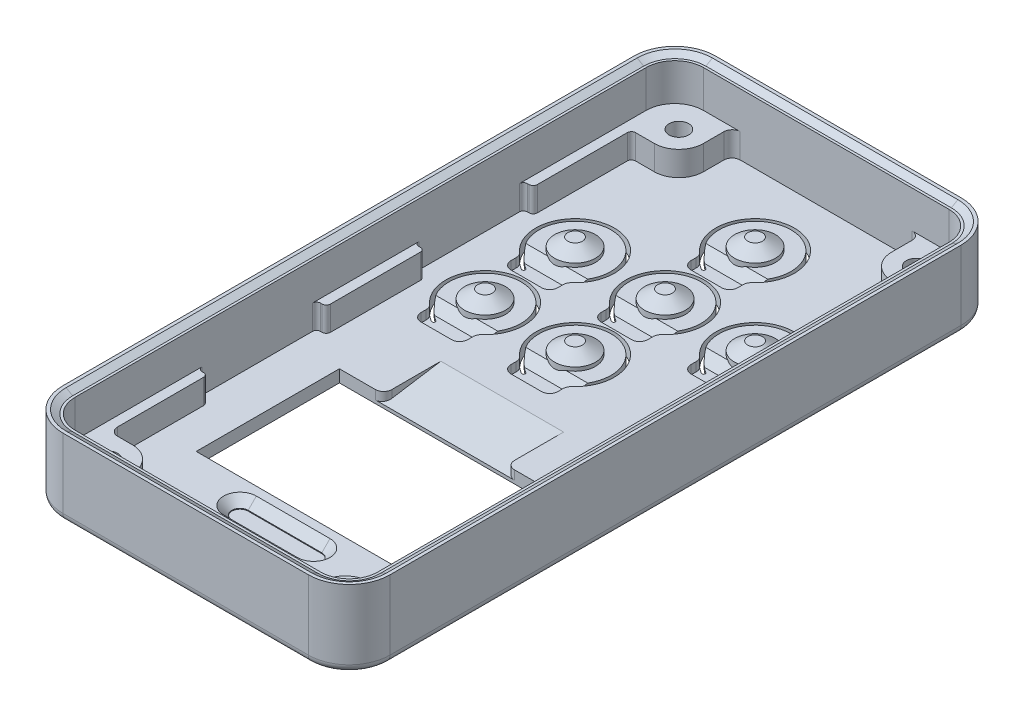
SolidWorks part; units mm, degrees
ref_plane "Front Plane" through (0, 0, 0) normal (0, 0, 1) x (1, 0, 0)
ref_plane "Top Plane" through (0, 0, 0) normal (0, 1, 0) x (1, 0, 0)
ref_plane "Right Plane" through (0, 0, 0) normal (1, 0, 0) x (0, 0, -1)
sketch "Base Sketch" plane through (0, 0, 0) normal (0, 1, 0) x (1, 0, 0)
  line L0 (0, 0) -> (40, 0)
  line L1 (40, 0) -> (40, 79.79)
  line L2 (40, 79.79) -> (0, 79.79)
  line L3 (0, 79.79) -> (0, 0)
extrude "Base" add sketch "Base Sketch" along normal blind 9.5
fillet "Corner Rounds R5" radius 5 4 edges at (0, 4.75, -79.79) (40, 4.75, -79.79) (40, 4.75, 0) (0, 4.75, 0)
shell "Shell 1.5" thickness 1.5 removed face at (20, 9.5, -39.895)
sketch "Boss Sketch" plane through (0, 0, 0) normal (0, 1, 0) x (1, 0, 0)
  line L0 (1.5, 1.5) -> (8.5, 1.5)
  line L1 (8.5, 1.5) -> (8.5, 5)
  line L2 (5.5, 8) -> (1.5, 8)
  line L3 (1.5, 8) -> (1.5, 1.5)
  line L4 (38.5, 1.5) -> (31.5, 1.5)
  line L5 (31.5, 1.5) -> (31.5, 5)
  line L6 (34.5, 8) -> (38.5, 8)
  line L7 (38.5, 8) -> (38.5, 1.5)
  line L16 (1.5, 78.29) -> (8.5, 78.29)
  line L17 (8.5, 78.29) -> (8.5, 74.79)
  line L18 (5.5, 71.79) -> (1.5, 71.79)
  line L19 (1.5, 71.79) -> (1.5, 78.29)
  line L20 (38.5, 78.29) -> (31.5, 78.29)
  line L21 (31.5, 78.29) -> (31.5, 74.79)
  line L22 (34.5, 71.79) -> (38.5, 71.79)
  line L23 (38.5, 71.79) -> (38.5, 78.29)
  arc A0 (8.5, 5) -> (5.5, 8) centre (5.4999, 4.9999) ccw
  circle A1 centre (5.5, 5) radius 1
  arc A2 (31.5, 5) -> (34.5, 8) centre (34.5001, 4.9999) cw
  circle A3 centre (34.5, 5) radius 1
  circle A5 centre (5.5, 74.79) radius 1
  circle A7 centre (34.5, 74.79) radius 1
  arc A8 (8.5, 74.79) -> (5.5, 71.79) centre (5.4999, 74.7901) cw
  arc A9 (31.5, 74.79) -> (34.5, 71.79) centre (34.5001, 74.7901) ccw
extrude "Corner Bosses (stop at ledge y4.5) + M2 Holes" add sketch "Boss Sketch" along normal blind 4.5
sketch "Ledge Sketch" plane through (0, 0, 0) normal (0, 1, 0) x (1, 0, 0)
  line L0 (1.5, 8) -> (2.7, 8)
  line L1 (2.7, 8) -> (2.7, 20)
  line L2 (2.7, 20) -> (1.5, 20)
  line L3 (1.5, 20) -> (1.5, 8)
  line L4 (37.3, 8) -> (38.5, 8)
  line L5 (38.5, 8) -> (38.5, 20)
  line L6 (38.5, 20) -> (37.3, 20)
  line L7 (37.3, 20) -> (37.3, 8)
  line L8 (1.5, 34.5) -> (2.7, 34.5)
  line L9 (2.7, 34.5) -> (2.7, 46.5)
  line L10 (2.7, 46.5) -> (1.5, 46.5)
  line L11 (1.5, 46.5) -> (1.5, 34.5)
  line L12 (37.3, 34.5) -> (38.5, 34.5)
  line L13 (38.5, 34.5) -> (38.5, 46.5)
  line L14 (38.5, 46.5) -> (37.3, 46.5)
  line L15 (37.3, 46.5) -> (37.3, 34.5)
  line L16 (1.5, 59.79) -> (2.7, 59.79)
  line L17 (2.7, 59.79) -> (2.7, 71.79)
  line L18 (2.7, 71.79) -> (1.5, 71.79)
  line L19 (1.5, 71.79) -> (1.5, 59.79)
  line L20 (37.3, 59.79) -> (38.5, 59.79)
  line L21 (38.5, 59.79) -> (38.5, 71.79)
  line L22 (38.5, 71.79) -> (37.3, 71.79)
  line L23 (37.3, 71.79) -> (37.3, 59.79)
extrude "Side Ledges" add sketch "Ledge Sketch" along normal blind 4.5
fillet "Outer Face Round R1" radius 1 8 edges at (1.4645, 0, -1.4645) (20, 0, 0) (38.5355, 0, -1.4645) (40, 0, -39.895) (38.5355, 0, -78.3255) (20, 0, -79.79) (1.4645, 0, -78.3255) (0, 0, -39.895)
sketch "Window Sketch" plane through (0, 0, 0) normal (0, 1, 0) x (1, 0, 0)
  line L0 (7.1, 14.5) -> (32.9, 14.5)
  line L1 (32.9, 14.5) -> (32.9, 31.7)
  line L2 (32.9, 31.7) -> (7.1, 31.7)
  line L3 (7.1, 31.7) -> (7.1, 14.5)
extrude "Display Window" cut sketch "Window Sketch" along normal through all
ref_plane "Mid Plane X20" through (20, 0, 0) normal (1, 0, 0) x (0, 0, -1)
sketch "Ramp Sketch" plane through (20, 0, 0) normal (1, 0, 0) x (0, 0, -1)
  line L0 (31, 0.4) -> (31.7, 0.4)
  line L1 (31.7, 0.4) -> (38.7, 1.5)
  line L2 (38.7, 1.5) -> (38.7, 2.5)
  line L3 (38.7, 2.5) -> (31, 2.5)
  line L4 (31, 2.5) -> (31, 0.4)
extrude "Cable Ramp" cut sketch "Ramp Sketch" against normal blind 7.5 and the other way blind 7.5
ref_plane "Plate Inner Face" through (0, 1.5, 0) normal (0, 1, 0) x (1, 0, 0)
sketch "LED Window Sketch" plane through (0, 1.5, 0) normal (0, 1, 0) x (1, 0, 0)
  circle A0 centre (20, 7.28) radius 1.7
  dimension "D1" = 3.4
extrude "LED Window" cut sketch "LED Window Sketch" against normal blind 1.1
sketch "Plunger Stems Sketch" plane through (0, 1.5, 0) normal (0, 1, 0) x (1, 0, 0)
  circle A0 centre (9, 47.6) radius 2.5
  circle A1 centre (20, 47.6) radius 2.5
  circle A2 centre (9, 58.6) radius 2.5
  circle A3 centre (20, 58.6) radius 2.5
  circle A4 centre (31, 58.6) radius 2.5
  circle A5 centre (20, 69.6) radius 2.5
extrude "Plunger Stems 5.0" add sketch "Plunger Stems Sketch" along normal blind 0.45
ref_plane "Plunger Cone Base" through (0, 1.95, 0) normal (0, 1, 0) x (1, 0, 0)
sketch "Plunger Cone Sketch" plane through (0, 1.95, 0) normal (0, 1, 0) x (1, 0, 0)
  circle A0 centre (9, 47.6) radius 2.5
  circle A1 centre (20, 47.6) radius 2.5
  circle A2 centre (9, 58.6) radius 2.5
  circle A3 centre (20, 58.6) radius 2.5
  circle A4 centre (31, 58.6) radius 2.5
  circle A5 centre (20, 69.6) radius 2.5
extrude "Plunger Cones to 1.8" add sketch "Plunger Cone Sketch" along normal blind 1 draft 57.995
fillet "Boss Junction Fillets R1" radius 1 7 edges at (37.3, 3, -71.79) (37.3, 3, -8) (2.7, 3, -8) (31.5, 3, -78.29) (8.5, 3, -78.29) (31.5, 3, -1.5) (8.5, 3, -1.5)
sketch "C-Slot Sketch" plane through (0, 0, 0) normal (0, 1, 0) x (1, 0, 0)
  arc A0 (10.4434, 43.0222) -> (7.5566, 43.0222) centre (9, 47.6) ccw
  arc A1 (7.5566, 43.0222) -> (7.6769, 43.4036) centre (7.6168, 43.2129) ccw
  arc A2 (7.6769, 43.4036) -> (10.3231, 43.4036) centre (9, 47.6) cw
  arc A3 (10.3231, 43.4036) -> (10.4434, 43.0222) centre (10.3832, 43.2129) ccw
  arc A4 (21.4434, 43.0222) -> (18.5566, 43.0222) centre (20, 47.6) ccw
  arc A5 (18.5566, 43.0222) -> (18.6769, 43.4036) centre (18.6168, 43.2129) ccw
  arc A6 (18.6769, 43.4036) -> (21.3231, 43.4036) centre (20, 47.6) cw
  arc A7 (21.3231, 43.4036) -> (21.4434, 43.0222) centre (21.3832, 43.2129) ccw
  arc A8 (10.4434, 54.0222) -> (7.5566, 54.0222) centre (9, 58.6) ccw
  arc A9 (7.5566, 54.0222) -> (7.6769, 54.4036) centre (7.6168, 54.2129) ccw
  arc A10 (7.6769, 54.4036) -> (10.3231, 54.4036) centre (9, 58.6) cw
  arc A11 (10.3231, 54.4036) -> (10.4434, 54.0222) centre (10.3832, 54.2129) ccw
  arc A12 (21.4434, 54.0222) -> (18.5566, 54.0222) centre (20, 58.6) ccw
  arc A13 (18.5566, 54.0222) -> (18.6769, 54.4036) centre (18.6168, 54.2129) ccw
  arc A14 (18.6769, 54.4036) -> (21.3231, 54.4036) centre (20, 58.6) cw
  arc A15 (21.3231, 54.4036) -> (21.4434, 54.0222) centre (21.3832, 54.2129) ccw
  arc A16 (32.4434, 54.0222) -> (29.5566, 54.0222) centre (31, 58.6) ccw
  arc A17 (29.5566, 54.0222) -> (29.6769, 54.4036) centre (29.6168, 54.2129) ccw
  arc A18 (29.6769, 54.4036) -> (32.3231, 54.4036) centre (31, 58.6) cw
  arc A19 (32.3231, 54.4036) -> (32.4434, 54.0222) centre (32.3832, 54.2129) ccw
  arc A20 (21.4434, 65.0222) -> (18.5566, 65.0222) centre (20, 69.6) ccw
  arc A21 (18.5566, 65.0222) -> (18.6769, 65.4036) centre (18.6168, 65.2129) ccw
  arc A22 (18.6769, 65.4036) -> (21.3231, 65.4036) centre (20, 69.6) cw
  arc A23 (21.3231, 65.4036) -> (21.4434, 65.0222) centre (21.3832, 65.2129) ccw
sketch "Sketch10" plane through (0, 1.5, 0) normal (0, 1, 0) x (1, 0, 0)
  line L0 (11.864, 44.259) -> (11.864, 41.636)
  line L1 (11.864, 41.636) -> (6.136, 41.636)
  line L2 (6.136, 41.636) -> (6.136, 44.259)
  line L3 (6.136, 44.259) -> (11.864, 44.259)
  line L4 (22.864, 44.259) -> (22.864, 41.636)
  line L5 (22.864, 41.636) -> (17.136, 41.636)
  line L6 (17.136, 41.636) -> (17.136, 44.259)
  line L7 (17.136, 44.259) -> (22.864, 44.259)
  line L8 (11.864, 55.259) -> (11.864, 52.636)
  line L9 (11.864, 52.636) -> (6.136, 52.636)
  line L10 (6.136, 52.636) -> (6.136, 55.259)
  line L11 (6.136, 55.259) -> (11.864, 55.259)
  line L12 (22.864, 55.259) -> (22.864, 52.636)
  line L13 (22.864, 52.636) -> (17.136, 52.636)
  line L14 (17.136, 52.636) -> (17.136, 55.259)
  line L15 (17.136, 55.259) -> (22.864, 55.259)
  line L16 (33.864, 55.259) -> (33.864, 52.636)
  line L17 (33.864, 52.636) -> (28.136, 52.636)
  line L18 (28.136, 52.636) -> (28.136, 55.259)
  line L19 (28.136, 55.259) -> (33.864, 55.259)
  line L20 (22.864, 66.259) -> (22.864, 63.636)
  line L21 (22.864, 63.636) -> (17.136, 63.636)
  line L22 (17.136, 63.636) -> (17.136, 66.259)
  line L23 (17.136, 66.259) -> (22.864, 66.259)
extrude "Cut-Extrude7" cut sketch "Sketch10" against normal blind 1.1
sketch "Sketch11" plane through (0, 0, 0) normal (0, 1, 0) x (1, 0, 0)
  arc A0 (11.4, 43.4431) -> (6.6, 43.4431) centre (9, 47.6) ccw
  arc A1 (6.6, 43.4431) -> (6.8, 43.7895) centre (6.7, 43.6163) ccw
  arc A2 (6.8, 43.7895) -> (11.2, 43.7895) centre (9, 47.6) cw
  arc A3 (11.2, 43.7895) -> (11.4, 43.4431) centre (11.3, 43.6163) ccw
  arc A4 (22.4, 43.4431) -> (17.6, 43.4431) centre (20, 47.6) ccw
  arc A5 (17.6, 43.4431) -> (17.8, 43.7895) centre (17.7, 43.6163) ccw
  arc A6 (17.8, 43.7895) -> (22.2, 43.7895) centre (20, 47.6) cw
  arc A7 (22.2, 43.7895) -> (22.4, 43.4431) centre (22.3, 43.6163) ccw
  arc A8 (11.4, 54.4431) -> (6.6, 54.4431) centre (9, 58.6) ccw
  arc A9 (6.6, 54.4431) -> (6.8, 54.7895) centre (6.7, 54.6163) ccw
  arc A10 (6.8, 54.7895) -> (11.2, 54.7895) centre (9, 58.6) cw
  arc A11 (11.2, 54.7895) -> (11.4, 54.4431) centre (11.3, 54.6163) ccw
  arc A12 (22.4, 54.4431) -> (17.6, 54.4431) centre (20, 58.6) ccw
  arc A13 (17.6, 54.4431) -> (17.8, 54.7895) centre (17.7, 54.6163) ccw
  arc A14 (17.8, 54.7895) -> (22.2, 54.7895) centre (20, 58.6) cw
  arc A15 (22.2, 54.7895) -> (22.4, 54.4431) centre (22.3, 54.6163) ccw
  arc A16 (33.4, 54.4431) -> (28.6, 54.4431) centre (31, 58.6) ccw
  arc A17 (28.6, 54.4431) -> (28.8, 54.7895) centre (28.7, 54.6163) ccw
  arc A18 (28.8, 54.7895) -> (33.2, 54.7895) centre (31, 58.6) cw
  arc A19 (33.2, 54.7895) -> (33.4, 54.4431) centre (33.3, 54.6163) ccw
  arc A20 (22.4, 65.4431) -> (17.6, 65.4431) centre (20, 69.6) ccw
  arc A21 (17.6, 65.4431) -> (17.8, 65.7895) centre (17.7, 65.6163) ccw
  arc A22 (17.8, 65.7895) -> (22.2, 65.7895) centre (20, 69.6) cw
  arc A23 (22.2, 65.7895) -> (22.4, 65.4431) centre (22.3, 65.6163) ccw
extrude "Button C-Slots 300deg 0.4" cut sketch "Sketch11" along normal through all
chamfer "Chamfer1" distance 1.1 angle 45 6 edges at (9, 1.5, -44.259) (20, 1.5, -66.259) (31, 1.5, -55.259) (20, 1.5, -55.259) (9, 1.5, -55.259) (20, 1.5, -44.259)
fillet "Fillet1" radius 1 24 edges at (11.864, 0.95, -43.7481) (11.864, 0.95, -41.636) (6.136, 0.95, -41.636) (6.136, 0.95, -43.7481) (22.864, 0.95, -63.636) (22.864, 0.95, -65.7481) (17.136, 0.95, -63.636) (17.136, 0.95, -65.7481) (33.864, 0.95, -52.636) (33.864, 0.95, -54.7481) (28.136, 0.95, -52.636) (28.136, 0.95, -54.7481) (22.864, 0.95, -52.636) (22.864, 0.95, -54.7481) (17.136, 0.95, -52.636) (17.136, 0.95, -54.7481) (11.864, 0.95, -52.636) (11.864, 0.95, -54.7481) (6.136, 0.95, -52.636) (6.136, 0.95, -54.7481) (22.864, 0.95, -41.636) (22.864, 0.95, -43.7481) (17.136, 0.95, -41.636) (17.136, 0.95, -43.7481)
fillet "Fillet2" radius 0.5 17 edges at (2.7, 3, -71.79) (1.5, 3, -59.79) (2.7, 3, -59.79) (38.5, 3, -59.79) (37.3, 3, -59.79) (38.5, 3, -46.5) (37.3, 3, -46.5) (2.7, 3, -46.5) (1.5, 3, -46.5) (38.5, 3, -34.5) (37.3, 3, -34.5) (2.7, 3, -34.5) (1.5, 3, -34.5) (38.5, 3, -20) (37.3, 3, -20) (2.7, 3, -20) (1.5, 3, -20)
fillet "Fillet3" radius 1 2 edges at (27.5, 0.95, -31.7) (12.5, 0.95, -31.7)
sketch "Button Symbols Cut Sketch" plane through (0, 0, 0) normal (0, 1, 0) x (1, 0, 0)
  line L0 (7.0908, 45.6908) -> (7.7272, 46.3272)
  line L1 (10.2728, 46.3272) -> (10.9092, 45.6908)
  line L2 (8.55, 47.2) -> (9.45, 47.2)
  line L3 (9.45, 47.2) -> (9.45, 44.4)
  line L4 (9.45, 44.4) -> (8.55, 44.4)
  line L5 (8.55, 44.4) -> (8.55, 47.2)
  line L6 (20, 44.8) -> (22.4249, 49)
  line L7 (22.4249, 49) -> (17.5751, 49)
  line L8 (17.5751, 49) -> (20, 44.8)
  line L9 (6.2, 58.6) -> (10.4, 56.1751)
  line L10 (10.4, 56.1751) -> (10.4, 61.0249)
  line L11 (10.4, 61.0249) -> (6.2, 58.6)
  line L12 (33.8, 58.6) -> (29.6, 61.0249)
  line L13 (29.6, 61.0249) -> (29.6, 56.1751)
  line L14 (29.6, 56.1751) -> (33.8, 58.6)
  line L15 (20, 72.4) -> (17.5751, 68.2)
  line L16 (17.5751, 68.2) -> (22.4249, 68.2)
  line L17 (22.4249, 68.2) -> (20, 72.4)
  arc A0 (10.9092, 45.6908) -> (7.0908, 45.6908) centre (9, 47.6) ccw
  arc A1 (7.7272, 46.3272) -> (10.2728, 46.3272) centre (9, 47.6) cw
  circle A2 centre (20, 58.6) radius 2.4
  circle A3 centre (20, 58.6) radius 1.5
sketch "Button Symbols Inlay Sketch" plane through (0, 0, 0) normal (0, 1, 0) x (1, 0, 0)
  line L0 (7.0908, 45.6908) -> (7.7272, 46.3272)
  line L1 (10.2728, 46.3272) -> (10.9092, 45.6908)
  line L2 (8.55, 47.2) -> (9.45, 47.2)
  line L3 (9.45, 47.2) -> (9.45, 44.4)
  line L4 (9.45, 44.4) -> (8.55, 44.4)
  line L5 (8.55, 44.4) -> (8.55, 47.2)
  line L6 (20, 44.8) -> (22.4249, 49)
  line L7 (22.4249, 49) -> (17.5751, 49)
  line L8 (17.5751, 49) -> (20, 44.8)
  line L9 (6.2, 58.6) -> (10.4, 56.1751)
  line L10 (10.4, 56.1751) -> (10.4, 61.0249)
  line L11 (10.4, 61.0249) -> (6.2, 58.6)
  line L12 (33.8, 58.6) -> (29.6, 61.0249)
  line L13 (29.6, 61.0249) -> (29.6, 56.1751)
  line L14 (29.6, 56.1751) -> (33.8, 58.6)
  line L15 (20, 72.4) -> (17.5751, 68.2)
  line L16 (17.5751, 68.2) -> (22.4249, 68.2)
  line L17 (22.4249, 68.2) -> (20, 72.4)
  arc A0 (10.9092, 45.6908) -> (7.0908, 45.6908) centre (9, 47.6) ccw
  arc A1 (7.7272, 46.3272) -> (10.2728, 46.3272) centre (9, 47.6) cw
  circle A2 centre (20, 58.6) radius 2.4
  circle A3 centre (20, 58.6) radius 1.5
sketch "Sketch14" plane through (0, 0, 0) normal (0, 1, 0) x (1, 0, 0)
  line L0 (8.4, 47) -> (8.4, 45.2)
  line L1 (9.6, 45.2) -> (9.6, 47)
  line L2 (20.5196, 44.9) -> (22.7713, 48.8)
  line L3 (22.2517, 49.7) -> (17.7483, 49.7)
  line L4 (17.2287, 48.8) -> (19.4804, 44.9)
  line L5 (6.1, 58.0804) -> (10, 55.8287)
  line L6 (10.9, 56.3483) -> (10.9, 60.8517)
  line L7 (10, 61.3713) -> (6.1, 59.1196)
  line L8 (33.9, 59.1196) -> (30, 61.3713)
  line L9 (29.1, 60.8517) -> (29.1, 56.3483)
  line L10 (30, 55.8287) -> (33.9, 58.0804)
  line L11 (19.4804, 72.5) -> (17.2287, 68.6)
  line L12 (17.7483, 67.7) -> (22.2517, 67.7)
  line L13 (22.7713, 68.6) -> (20.5196, 72.5)
  arc A0 (11.4513, 45.5431) -> (6.5487, 45.5431) centre (9, 47.6) ccw
  arc A1 (6.5487, 45.5431) -> (7.4679, 46.3144) centre (7.0083, 45.9288) ccw
  arc A2 (7.4679, 46.3144) -> (10.5321, 46.3144) centre (9, 47.6) cw
  arc A3 (10.5321, 46.3144) -> (11.4513, 45.5431) centre (10.9917, 45.9288) ccw
  arc A4 (8.4, 45.2) -> (9.6, 45.2) centre (9, 45.2) ccw
  arc A5 (9.6, 47) -> (8.4, 47) centre (9, 47) ccw
  arc A6 (19.4804, 44.9) -> (20.5196, 44.9) centre (20, 45.2) ccw
  arc A7 (22.7713, 48.8) -> (22.2517, 49.7) centre (22.2517, 49.1) ccw
  arc A8 (17.7483, 49.7) -> (17.2287, 48.8) centre (17.7483, 49.1) ccw
  arc A9 (6.1, 59.1196) -> (6.1, 58.0804) centre (6.4, 58.6) ccw
  arc A10 (10, 55.8287) -> (10.9, 56.3483) centre (10.3, 56.3483) ccw
  arc A11 (10.9, 60.8517) -> (10, 61.3713) centre (10.3, 60.8517) ccw
  circle A12 centre (20, 58.6) radius 3.1
  circle A13 centre (20, 58.6) radius 1.9
  arc A14 (33.9, 58.0804) -> (33.9, 59.1196) centre (33.6, 58.6) ccw
  arc A15 (30, 61.3713) -> (29.1, 60.8517) centre (29.7, 60.8517) ccw
  arc A16 (29.1, 56.3483) -> (30, 55.8287) centre (29.7, 56.3483) ccw
  arc A17 (20.5196, 72.5) -> (19.4804, 72.5) centre (20, 72.2) ccw
  arc A18 (17.2287, 68.6) -> (17.7483, 67.7) centre (17.7483, 68.3) ccw
  arc A19 (22.2517, 67.7) -> (22.7713, 68.6) centre (22.2517, 68.3) ccw
extrude "Button Symbol Recess 0.4" cut sketch "Sketch14" along normal blind 0.4
sketch "Sketch15" plane through (0, 0, 0) normal (0, 1, 0) x (1, 0, 0)
  line L0 (8.4, 47) -> (8.4, 45.2)
  line L1 (9.6, 45.2) -> (9.6, 47)
  line L2 (20.5196, 44.9) -> (22.7713, 48.8)
  line L3 (22.2517, 49.7) -> (17.7483, 49.7)
  line L4 (17.2287, 48.8) -> (19.4804, 44.9)
  line L5 (6.1, 58.0804) -> (10, 55.8287)
  line L6 (10.9, 56.3483) -> (10.9, 60.8517)
  line L7 (10, 61.3713) -> (6.1, 59.1196)
  line L8 (33.9, 59.1196) -> (30, 61.3713)
  line L9 (29.1, 60.8517) -> (29.1, 56.3483)
  line L10 (30, 55.8287) -> (33.9, 58.0804)
  line L11 (19.4804, 72.5) -> (17.2287, 68.6)
  line L12 (17.7483, 67.7) -> (22.2517, 67.7)
  line L13 (22.7713, 68.6) -> (20.5196, 72.5)
  arc A0 (11.4513, 45.5431) -> (6.5487, 45.5431) centre (9, 47.6) ccw
  arc A1 (6.5487, 45.5431) -> (7.4679, 46.3144) centre (7.0083, 45.9288) ccw
  arc A2 (7.4679, 46.3144) -> (10.5321, 46.3144) centre (9, 47.6) cw
  arc A3 (10.5321, 46.3144) -> (11.4513, 45.5431) centre (10.9917, 45.9288) ccw
  arc A4 (8.4, 45.2) -> (9.6, 45.2) centre (9, 45.2) ccw
  arc A5 (9.6, 47) -> (8.4, 47) centre (9, 47) ccw
  arc A6 (19.4804, 44.9) -> (20.5196, 44.9) centre (20, 45.2) ccw
  arc A7 (22.7713, 48.8) -> (22.2517, 49.7) centre (22.2517, 49.1) ccw
  arc A8 (17.7483, 49.7) -> (17.2287, 48.8) centre (17.7483, 49.1) ccw
  arc A9 (6.1, 59.1196) -> (6.1, 58.0804) centre (6.4, 58.6) ccw
  arc A10 (10, 55.8287) -> (10.9, 56.3483) centre (10.3, 56.3483) ccw
  arc A11 (10.9, 60.8517) -> (10, 61.3713) centre (10.3, 60.8517) ccw
  circle A12 centre (20, 58.6) radius 3.1
  circle A13 centre (20, 58.6) radius 1.9
  arc A14 (33.9, 58.0804) -> (33.9, 59.1196) centre (33.6, 58.6) ccw
  arc A15 (30, 61.3713) -> (29.1, 60.8517) centre (29.7, 60.8517) ccw
  arc A16 (29.1, 56.3483) -> (30, 55.8287) centre (29.7, 56.3483) ccw
  arc A17 (20.5196, 72.5) -> (19.4804, 72.5) centre (20, 72.2) ccw
  arc A18 (17.2287, 68.6) -> (17.7483, 67.7) centre (17.7483, 68.3) ccw
  arc A19 (22.2517, 67.7) -> (22.7713, 68.6) centre (22.2517, 68.3) ccw
extrude "Button Symbol Inlays 0.4 (colour 2)" add sketch "Sketch15" along normal blind 0.4 separate body
sketch "I2C Header Pocket Sketch" plane through (0, 1.5, 0) normal (0, 1, 0) x (1, 0, 0)
  line L0 (15.5, 9.4) -> (24.5, 9.4)
  line L1 (25.5, 10.4) -> (25.5, 11.9)
  line L2 (24.5, 12.9) -> (15.5, 12.9)
  line L3 (14.5, 11.9) -> (14.5, 10.4)
  line L4 (32.9, 14.5) -> (7.1, 14.5) construction
  arc A0 (24.5, 9.4) -> (25.5, 10.4) centre (24.5, 10.4) ccw
  arc A1 (25.5, 11.9) -> (24.5, 12.9) centre (24.5, 11.9) ccw
  arc A2 (15.5, 12.9) -> (14.5, 11.9) centre (15.5, 11.9) ccw
  arc A3 (14.5, 10.4) -> (15.5, 9.4) centre (15.5, 10.4) ccw
  dimension "D3" = 1
  dimension "D1" = 1.6
  dimension "D2" = 11
  dimension "D4" = 2.6
sketch "Sketch17" plane through (0, 1.5, 0) normal (0, 1, 0) x (1, 0, 0)
  line L0 (15.2, 10.45) -> (24.8, 10.45)
  line L1 (24.8, 11.85) -> (15.2, 11.85)
  arc A0 (24.8, 10.45) -> (24.8, 11.85) centre (24.8, 11.15) ccw
  arc A1 (15.2, 11.85) -> (15.2, 10.45) centre (15.2, 11.15) ccw
sketch "Sketch18" plane through (0, 0, -14.5) normal (0, 0, -1) x (-1, 0, 0)
  line L4 (-32.9, 1.5) -> (-32.9, 0)
  line L5 (-32.9, 0) -> (-7.1, 0)
  line L6 (-7.1, 0) -> (-7.1, 1.5)
  line L7 (-7.1, 1.5) -> (-32.9, 1.5)
  line L8 (-32.9, 1.5) -> (-32.9, 0)
  line L9 (-32.9, 0) -> (-7.1, 0)
  line L10 (-7.1, 0) -> (-7.1, 1.5)
  line L11 (-7.1, 1.5) -> (-32.9, 1.5)
  dimension "D1" = 0
extrude "Cut-Extrude16" cut sketch "Sketch18" against normal blind 0.3
sketch "Sketch19" plane through (0, 1.5, 0) normal (0, 1, 0) x (1, 0, 0)
  line L0 (15.2999, 10.35) -> (24.7001, 10.35)
  line L1 (25.5, 11.1499) -> (25.5, 11.1501)
  line L2 (24.7001, 11.95) -> (15.2999, 11.95)
  line L3 (14.5, 11.1501) -> (14.5, 11.1499)
  arc A0 (24.7001, 10.35) -> (25.5, 11.1499) centre (24.7001, 11.1499) ccw
  arc A1 (25.5, 11.1501) -> (24.7001, 11.95) centre (24.7001, 11.1501) ccw
  arc A2 (15.2999, 11.95) -> (14.5, 11.1501) centre (15.2999, 11.1501) ccw
  arc A3 (14.5, 11.1499) -> (15.2999, 10.35) centre (15.2999, 11.1499) ccw
sketch "Sketch20" plane through (0, 1.5, 0) normal (0, 1, 0) x (1, 0, 0)
  line L0 (15.5, 10.15) -> (24.5, 10.15)
  line L1 (24.5, 12.15) -> (15.5, 12.15)
  arc A0 (24.5, 10.15) -> (24.5, 12.15) centre (24.5, 11.15) ccw
  arc A1 (15.5, 12.15) -> (15.5, 10.15) centre (15.5, 11.15) ccw
extrude "I2C Header Lead Pocket 2.0 (0.2 skin)" cut sketch "Sketch20" against normal blind 1.1
chamfer "Chamfer3" distance 1 angle 45 4 edges at (20, 1.5, -12.15) (14.5, 1.5, -11.15) (25.5, 1.5, -11.15) (20, 1.5, -10.15)
sketch "Sketch21" plane through (0, 0, 0) normal (0, -1, 0) x (1, 0, 0)
  circle A0 centre (20, -7.28) radius 2.5
  circle A1 centre (20, -7.28) radius 1.7
  circle A2 centre (20, -7.28) radius 1.7 construction
  circle A3 centre (20, -7.28) radius 2.6
  dimension "D2" = 5
  dimension "D3" = 0.1
  dimension "D1" = 0
extrude "Cut-Extrude17" cut sketch "Sketch21" against normal blind 0.1
sketch "M2 Clearance 2.4 (screw from front) Sketch" plane through (0, 0, 0) normal (0, 1, 0) x (1, 0, 0)
  circle A0 centre (5.5, 5) radius 1.2
  circle A1 centre (34.5, 5) radius 1.2
  circle A2 centre (5.5, 74.79) radius 1.2
  circle A3 centre (34.5, 74.79) radius 1.2
extrude "M2 Clearance 2.4 (screw from front)" cut sketch "M2 Clearance 2.4 (screw from front) Sketch" along normal through all
sketch "M2 Head Counterbore 4.4 x 2.0 Sketch" plane through (0, 0, 0) normal (0, 1, 0) x (1, 0, 0)
  circle A0 centre (5.5, 5) radius 2.2
  circle A1 centre (34.5, 5) radius 2.2
  circle A2 centre (5.5, 74.79) radius 2.2
  circle A3 centre (34.5, 74.79) radius 2.2
extrude "M2 Head Counterbore 4.4 x 2.0" cut sketch "M2 Head Counterbore 4.4 x 2.0 Sketch" along normal blind 2
chamfer "M2 CSK Seats (head 1 mm below face)" distance 1 angle 45 4 edges at (34.5, 2, -72.59) (5.5, 2, -72.59) (34.5, 2, -2.8) (5.5, 2, -2.8)
ref_plane "Joint Bevel Plane" through (0, 9.0381, 0) normal (0, 1, 0) x (1, 0, 0)
sketch "Wall Bevel 30deg + 0.4 flats Sketch" plane through (0, 9.0381, 0) normal (0, 1, 0) x (1, 0, 0)
  line L0 (5, 1.2) -> (35, 1.2)
  line L1 (38.8, 5) -> (38.8, 74.79)
  line L2 (35, 78.59) -> (5, 78.59)
  line L3 (1.2, 74.79) -> (1.2, 5)
  arc A0 (35, 1.2) -> (38.8, 5) centre (35, 5) ccw
  arc A1 (38.8, 74.79) -> (35, 78.59) centre (35, 74.79) ccw
  arc A2 (5, 78.59) -> (1.2, 74.79) centre (5, 74.79) ccw
  arc A3 (1.2, 5) -> (5, 1.2) centre (5, 5) ccw
extrude "Wall Bevel 30deg + 0.4 flats" cut sketch "Wall Bevel 30deg + 0.4 flats Sketch" along normal blind 0.4619 draft 60 draft outward yes
